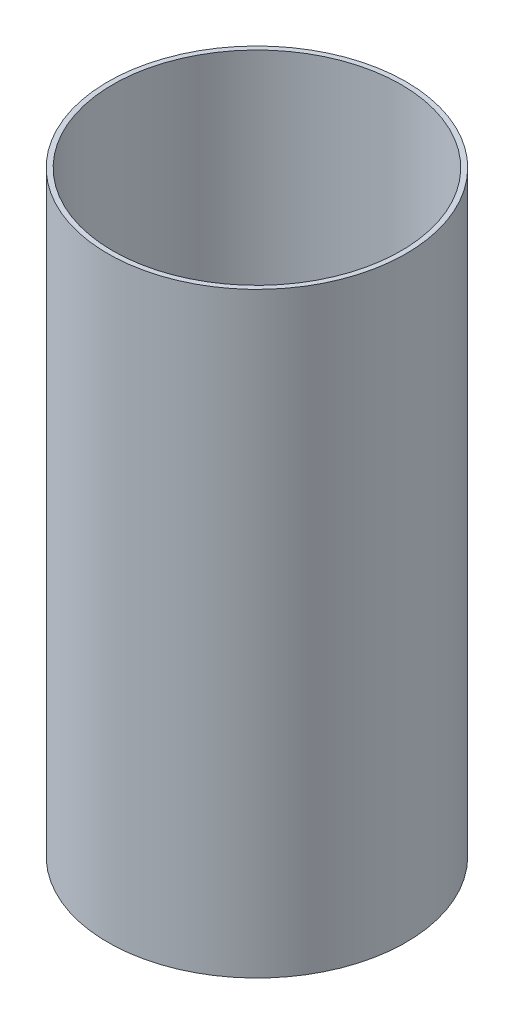
SolidWorks part; units mm, degrees
ref_plane "Front Plane" through (0, 0, 0) normal (0, 0, 1) x (1, 0, 0)
ref_plane "Top Plane" through (0, 0, 0) normal (0, 1, 0) x (1, 0, 0)
ref_plane "Right Plane" through (0, 0, 0) normal (1, 0, 0) x (0, 0, -1)
sketch "Sketch1" plane through (0, 0, 0) normal (0, 1, 0) x (1, 0, 0)
  circle A0 centre (0, 0) radius 76.1746
  circle A1 centre (0, 0) radius 73.66
  dimension "D1" = 152.3492
  dimension "D2" = 147.32
extrude "Boss-Extrude1" add sketch "Sketch1" along normal blind 304.8
equation "\"Mid_Coupler_Length\" = 12in"
equation "\"D1@Boss-Extrude1\"=\"Mid_Coupler_Length\""
